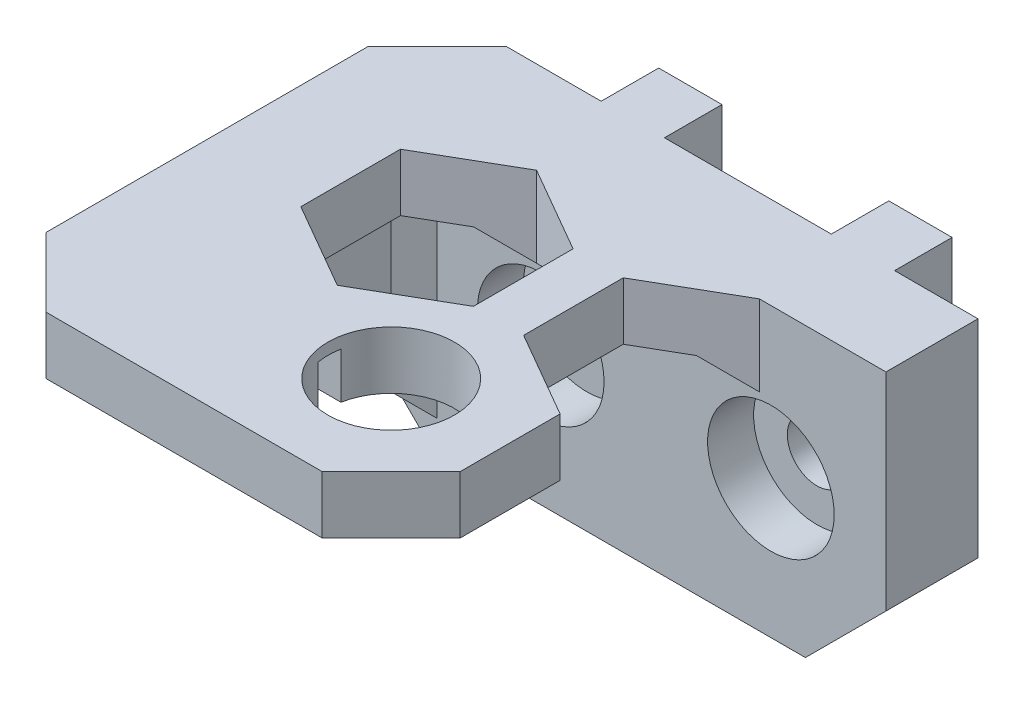
SolidWorks part; units mm, degrees
ref_plane "Front Plane" through (0, 0, 0) normal (0, 0, 1) x (1, 0, 0)
ref_plane "Top Plane" through (0, 0, 0) normal (0, 1, 0) x (1, 0, 0)
ref_plane "Right Plane" through (0, 0, 0) normal (1, 0, 0) x (0, 0, -1)
sketch "Sketch1" plane through (0, 0, 0) normal (0, 1, 0) x (1, 0, 0)
  line L0 (20, 20) -> (20, 12)
  line L1 (-27, 20) -> (20, 20)
  line L2 (-27, 20) -> (-27, -20)
  line L3 (-27, -20) -> (9, -20)
  line L5 (-27, 20) -> (27, -20) construction
  line L6 (-27, -20) -> (27, 20) construction
  line L9 (20, 12) -> (9, 12)
  line L10 (9, -20) -> (9, 12)
  point P0 (0, 0)
  dimension "D1" = 40
  dimension "D2" = 54
  dimension "D3" = 8
  dimension "D5" = 11
  dimension "D6" = 47
extrude "Boss-Extrude1" add sketch "Sketch1" along normal blind 5
sketch "Sketch3" plane through (0, 0, -20) normal (0, 0, -1) x (-1, 0, 0)
  line L0 (27, 5) -> (27, 0) construction
  line L1 (-20, 5) -> (27, 5)
  line L2 (-20, 5) -> (-20, -20)
  line L3 (-20, -20) -> (27, -20)
  line L4 (27, 5) -> (27, -20)
  line L5 (-20, 5) -> (-20, 0) construction
  dimension "D1" = 25
extrude "Boss-Extrude2" add sketch "Sketch3" against normal blind 8
sketch "Sketch9" plane through (-27, 0, 0) normal (-1, 0, 0) x (0, 0, 1)
  line L0 (-12, -18) -> (6, 0)
  line L1 (-12, -20) -> (-12, 0) construction
  line L2 (-12, 0) -> (20, 0) construction
  dimension "D1" = 18
  dimension "D2" = 18
rib "Rib2" sketch "Sketch9" sketch "Sketch9" thickness 6 extrusion direction parallel to sketch draft on no parameters "D1"=6
sketch "Sketch2" plane through (0, 5, 0) normal (0, 1, 0) x (1, 0, 0)
  line L0 (9, -20) -> (9, 12) construction
  line L1 (9, -5.3205) -> (16.5, -0.9904)
  line L2 (16.5, -0.9904) -> (16.5, 7.6699)
  line L3 (-27, 20) -> (-27, -20) construction
  line L4 (16.5, 7.6699) -> (9, 12)
  line L5 (20, 20) -> (-27, 20) construction
  line L6 (9, 12) -> (1.5, 7.6699)
  line L7 (1.5, 7.6699) -> (1.5, -0.9904)
  line L8 (1.5, -0.9904) -> (9, -5.3205)
  line L10 (-10.3622, -5.3205) -> (-2.8622, -0.9904)
  line L11 (-2.8622, -0.9904) -> (-2.8622, 7.6699)
  line L12 (-2.8622, 7.6699) -> (-10.3622, 12)
  line L13 (-10.3622, 12) -> (-17.8622, 7.6699)
  line L14 (-17.8622, 7.6699) -> (-17.8622, -0.9904)
  line L15 (-17.8622, -0.9904) -> (-10.3622, -5.3205)
  circle A0 centre (-1, -10) radius 5.5
  circle A1 centre (-18.5, -10) radius 4.2
  circle A2 centre (9, 3.3397) radius 7.5 construction
  circle A3 centre (-10.3622, 3.3397) radius 7.5 construction
  dimension "D1" = 11
  dimension "D2" = 8.4
  dimension "D5" = 15
  dimension "D3" = 17.5
  dimension "D7" = 26
  dimension "D8" = 30
extrude "Cut-Extrude1" cut sketch "Sketch2" against normal blind 5
sketch "Sketch4" plane through (0, 0, -12) normal (0, 0, 1) x (1, 0, 0)
  line L0 (-27, 5) -> (-27, -20) construction
  line L1 (20, 5) -> (-27, 5) construction
  circle A0 centre (-10, -8) radius 2.575
  circle A1 centre (10, -8) radius 2.575
  dimension "D3" = 13
  dimension "D4" = 5.15
  dimension "D1" = 20
  dimension "D2" = 17
extrude "Cut-Extrude2" cut sketch "Sketch4" against normal blind 8
sketch "Sketch11" plane through (0, 5, 0) normal (0, 1, 0) x (1, 0, 0)
  line L0 (-27, 20) -> (-27, -20) construction
  line L1 (-12.75, 20) -> (-7.25, 20)
  line L2 (-12.75, 20) -> (-12.75, 25)
  line L3 (-12.75, 25) -> (-7.25, 25)
  line L4 (-7.25, 20) -> (-7.25, 25)
  line L5 (20, 20) -> (-27, 20) construction
  line L6 (7.25, 20) -> (12.75, 20)
  line L7 (7.25, 20) -> (7.25, 25)
  line L8 (7.25, 25) -> (12.75, 25)
  line L9 (12.75, 20) -> (12.75, 25)
  point P16 (-10, 25)
  point P19 (10, 25)
  dimension "D1" = 5
  dimension "D2" = 5.5
  dimension "D3" = 20
  dimension "D4" = 17
extrude "Boss-Extrude5" add sketch "Sketch11" against normal blind 7
sketch "Sketch12" plane through (0, 5, 0) normal (0, 1, 0) x (1, 0, 0)
  circle A0 centre (-18.5, -10) radius 4.9411
extrude "Boss-Extrude6" add sketch "Sketch12" against normal blind 1
sketch "Sketch7" plane through (0, 0, -12) normal (0, 0, 1) x (1, 0, 0)
  circle A0 centre (-10, -8) radius 5.5
  circle A1 centre (10, -8) radius 5.5
  dimension "D1" = 11
extrude "Cut-Extrude3" cut sketch "Sketch7" against normal blind 4
sketch "Sketch10" plane through (0, 0, 0) normal (0, -1, 0) x (1, 0, 0)
  line L1 (-16.1431, 10.9653) -> (-5.0831, 10.9653)
  line L2 (-16.1431, 10.9653) -> (-16.1431, 8.9653)
  line L3 (-16.1431, 8.9653) -> (-5.0831, 8.9653)
  line L4 (-5.0831, 10.9653) -> (-5.0831, 8.9653)
  line L5 (-16.1431, 10.9653) -> (-5.0831, 8.9653) construction
  line L6 (-16.1431, 8.9653) -> (-5.0831, 10.9653) construction
  point P0 (-10.6131, 9.9653)
  dimension "D1" = 2
extrude "Cut-Extrude4" cut sketch "Sketch10" against normal blind 4
chamfer "Chamfer1" distance 6 angle 45 3 edges at (9, 2.5, 20) (-27, 2.5, 20) (-27, -7.5, -20)
chamfer "Chamfer2" distance 7 angle 45 2 edges at (-27, -20, -13) (20, -20, -16)
chamfer "Chamfer4" distance 2 angle 45 4 edges at (-0.6811, 0, -12) (-15.6811, 0, -12) (-21, 0, -3) (-21, -9, -12)
pattern_linear "LPattern1" count 2 spacing 18 along (0, -1, 0) of "Boss-Extrude5"
chamfer "Chamfer5" distance 2 angle 45 2 edges at (-10, -2, -25) (10, -2, -25)
chamfer "Chamfer6" distance 5 angle 45 2 edges at (-10, -13, -25) (10, -13, -25)
mirror "Mirror1" [suppressed] of bodies 108 104
delete or keep bodies "Body-Delete/Keep 1" [suppressed] type delete bodies bodies 108
